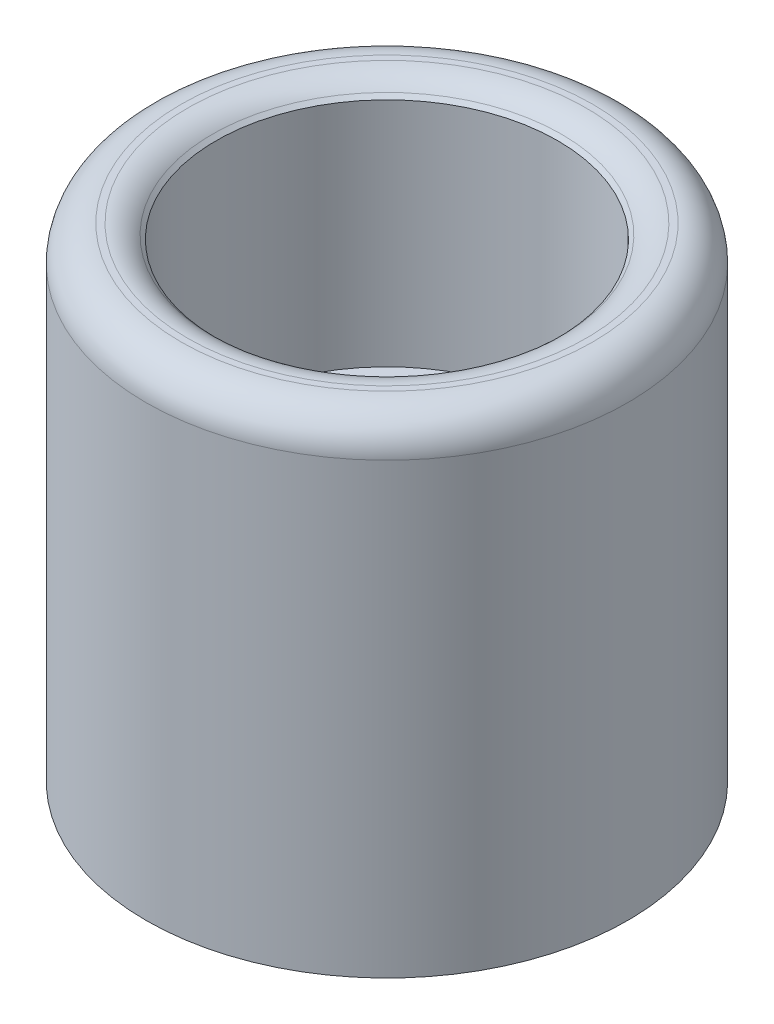
SolidWorks part; units mm, degrees
ref_plane "Front Plane" through (0, 0, 0) normal (0, 0, 1) x (1, 0, 0)
ref_plane "Top Plane" through (0, 0, 0) normal (0, 1, 0) x (1, 0, 0)
ref_plane "Right Plane" through (0, 0, 0) normal (1, 0, 0) x (0, 0, -1)
sketch "Sketch1" plane through (0, 0, 0) normal (0, 1, 0) x (1, 0, 0)
  circle A0 centre (0, 0) radius 24.384
  circle A1 centre (0, 0) radius 34.384
  dimension "D1" = 48.768
  dimension "D2" = 10
extrude "Boss-Extrude1" add sketch "Sketch1" along normal blind 35
extrude "Boss-Extrude2" add sketch "Sketch1<3>" against normal blind 34 contours A1 A0 | A0 region at (-33.4115, 0, 0)
sketch "Sketch1<3>" plane through (0, 0, 0) normal (0, 1, 0) x (1, 0, 0) same geometry as "Sketch1"
chamfer "Chamfer1" distance 2 angle 45 1 edges at (0, 35, 24.384)
fillet "Fillet2" radius 5 2 edges at (0, 35, 34.384) (0, 35, 26.384)
ref_plane "Plane1" through (0, -19, 0) normal (0, -1, 0) x (-1, 0, 0)
sketch "Sketch10" plane through (0, -19, 0) normal (0, -1, 0) x (-1, 0, 0)
  line L1 (7.7942, 0) -> (3.8971, 6.75)
  line L2 (3.8971, 6.75) -> (-3.8971, 6.75)
  line L3 (-3.8971, 6.75) -> (-7.7942, 0)
  line L4 (-7.7942, 0) -> (-3.8971, -6.75)
  line L5 (-3.8971, -6.75) -> (3.8971, -6.75)
  line L6 (3.8971, -6.75) -> (7.7942, 0)
  circle A0 centre (0, 0) radius 6.75 construction
  dimension "D1" = 13.5
extrude "Cut-Extrude1" cut sketch "Sketch10" along normal blind 7.1437
hole_wizard "Ø10.0mm Dowel Hole1" positions "Sketch13" profile "Sketch14" hole size "Ø10.0" standard "ANSI Metric" end condition through all
sketch "Sketch13" plane through (0, -34, 0) normal (0, -1, 0) x (-1, 0, 0)
  point P0 (0, 0)
sketch "Sketch14" plane through (0, -34, 0) normal (1, 0, 0) x (0, 0, -1)
  line L0 (0, 0) -> (0, 69)
  line L1 (0, 69) -> (5, 69)
  line L2 (5, 69) -> (5, 0)
  line L5 (5, 0) -> (0, 0)
  line L11 (0, -6.35) -> (0, 107.95) construction
  dimension "Thru Hole Dia." = 10
  dimension "Thru Hole Depth" = 69
